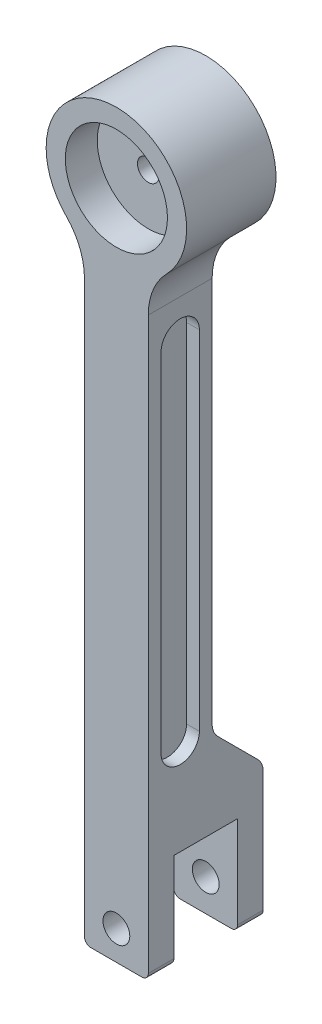
SolidWorks part; units mm, degrees
material "PLA 100% Infill"
ref_plane "Front Plane" through (0, 0, 0) normal (0, 0, 1) x (1, 0, 0)
ref_plane "Top Plane" through (0, 0, 0) normal (0, 1, 0) x (1, 0, 0)
ref_plane "Right Plane" through (0, 0, 0) normal (1, 0, 0) x (0, 0, -1)
sketch "Sketch1" plane through (0, 0, 0) normal (0, 0, 1) x (1, 0, 0)
  line L1 (0, 0) -> (-10, 0)
  line L2 (0, 0) -> (0, 95.2036)
  line L3 (0, 95.2036) -> (-10, 95.2036)
  line L4 (-10, 0) -> (-10, 95.2036)
  circle A0 centre (-5, 105.0016) radius 11
  circle A1 centre (-5, 105.0016) radius 8
  circle A2 centre (-5, 105.0016) radius 1.7
  dimension "D1" = 22
  dimension "D3" = 16
  dimension "D4" = 3.4
  dimension "D2" = 10
  dimension "D5" = 95.2036
extrude "Boss-Extrude1" add sketch "Sketch1" along normal blind 10 contours A0 L4 L1 L2 | L3 A0 A1 | L3 A0 region at (-5, 47.1972, 0) region at (-5, 94.7205, 0) region at (-5, 95.5063, 0)
extrude "Boss-Extrude2" add sketch "Sketch1<3>" along normal blind 5 contours A1 A2 region at (-12.7737, 105.0016, 0)
sketch "Sketch1<3>" plane through (0, 0, 0) normal (0, 0, 1) x (1, 0, 0) same geometry as "Sketch1"
sketch "Sketch2" plane through (0, 0, 0) normal (0, 0, -1) x (-1, 0, 0)
  circle A0 centre (5, 105.0016) radius 11
  circle A1 centre (5, 105.0016) radius 1.7 construction
  circle A2 centre (5, 105.0016) radius 1.7
extrude "Boss-Extrude3" add sketch "Sketch2" along normal blind 4
fillet "Fillet1" radius 10 2 edges at (-10, 95.2036, 5) (0, 95.2036, 5)
sketch "Sketch3" plane through (0, 0, 0) normal (1, 0, 0) x (0, 0, -1)
  line L0 (-5, 0) -> (-5, 90.3046) construction
  line L1 (-10, 0) -> (0, 0) construction
  line L2 (0, 90.3046) -> (-10, 90.3046) construction
  line L3 (0, 0) -> (0, 90.3046) construction
  line L4 (-10, 0) -> (-6, 0)
  line L5 (-6, 0) -> (-6, 15)
  line L7 (-6, 15) -> (4, 15)
  line L8 (-10, 0) -> (-10, 90.3046) construction
  line L9 (4, -0.4031) -> (4, 15)
  line L10 (4, -0.4031) -> (8, -0.4031)
  line L11 (8, 20.5969) -> (0, 28.5969)
  line L12 (8, -0.4031) -> (8, 20.5969)
  point P19 (-5, 15)
  line M7 (0, 0) -> (0, 90.3046)
  line M10 (-10, 0) -> (0, 0)
  dimension "D1" = 21
  dimension "D2" = 4
  dimension "D3" = 10
  dimension "D4" = 4
  dimension "D5" = 45
extrude "Boss-Extrude4" add sketch "Sketch3" against normal up to surface (10 mm away) contours L10 L12 L11 L7 L9 M7 region at (0, 14.3874, -4.5821) up to face at (-10, 45.1523, 5)
extrude "Cut-Extrude1" cut sketch "Sketch3<3>" against normal through all contours L0 L7 M10 M7 | L0 L7 L5 M10 region at (0, 7.5, 5.5) region at (0, 7.5, 2.5)
sketch "Sketch3<3>" plane through (0, 0, 0) normal (1, 0, 0) x (0, 0, -1) same geometry as "Sketch3"
fillet "Fillet2" radius 3 2 edges at (-5, 28.5969, 0) (-5, 20.5969, -8)
sketch "Sketch4" plane through (0, 0, 10) normal (0, 0, 1) x (1, 0, 0)
  line L0 (-5, 15.7574) -> (-5, -0.4031) construction
  line L3 (-10, -0.4031) -> (0, -0.4031) construction
  circle A0 centre (-5, 4.5969) radius 2.1
  dimension "D1" = 4.2
  dimension "D2" = 5
extrude "Cut-Extrude2" cut sketch "Sketch4" against normal through all
chamfer "Chamfer1" distance 3 angle 45 1 edges at (-10, 15, 1)
sketch "Sketch5" plane through (0, 0, 0) normal (1, 0, 0) x (0, 0, -1)
  line L2 (-10, 0) -> (-10, 90.3046) construction
  line L20 (-8, 29.8396) -> (-8, 84.3046)
  line L21 (-8, 84.3046) -> (-2, 84.3046) construction
  line L22 (-2, 29.8396) -> (-2, 90.3046)
  line L23 (-2, 29.8396) -> (-2, 84.3046)
  line L24 (0, 90.3046) -> (-10, 90.3046) construction
  arc A1 (-8, 84.3046) -> (-2, 84.3046) centre (-5, 84.3046) cw
  arc A2 (-8, 29.8396) -> (-2, 29.8396) centre (-5, 29.8396) ccw
  dimension "D1" = 2
  dimension "6" = 6
  dimension "D2" = 2
fillet "Fillet3" radius 1 4 edges at (-10, 0, 8) (0, 0, 8) (-10, -0.4031, -6) (0, -0.4031, -6)
extrude "Cut-Extrude3" cut sketch "Sketch5" against normal blind 2
ref_plane "Plane1" through (-5, 0, 0) normal (1, 0, 0) x (0, 0, -1)
mirror "Mirror1" about plane through (-5, 0, 0) normal (1, 0, 0) of "Cut-Extrude3"
ref_plane "Plane2" through (0, 90.3046, 0) normal (0, 1, 0) x (0, 0, 1)
ref_plane "Plane3" through (0, 0, -14) normal (0, 0, -1) x (-1, 0, 0)
sketch "Sketch6" plane through (0, 0, -4) normal (0, 0, -1) x (-1, 0, 0)
  circle A0 centre (5, 105.0016) radius 4.5
  dimension "D1" = 9
extrude "Cut-Extrude4" cut sketch "Sketch6" against normal blind 1
fillet "Fillet4" radius 1 1 edges at (-9.5, 105.0016, -3)
